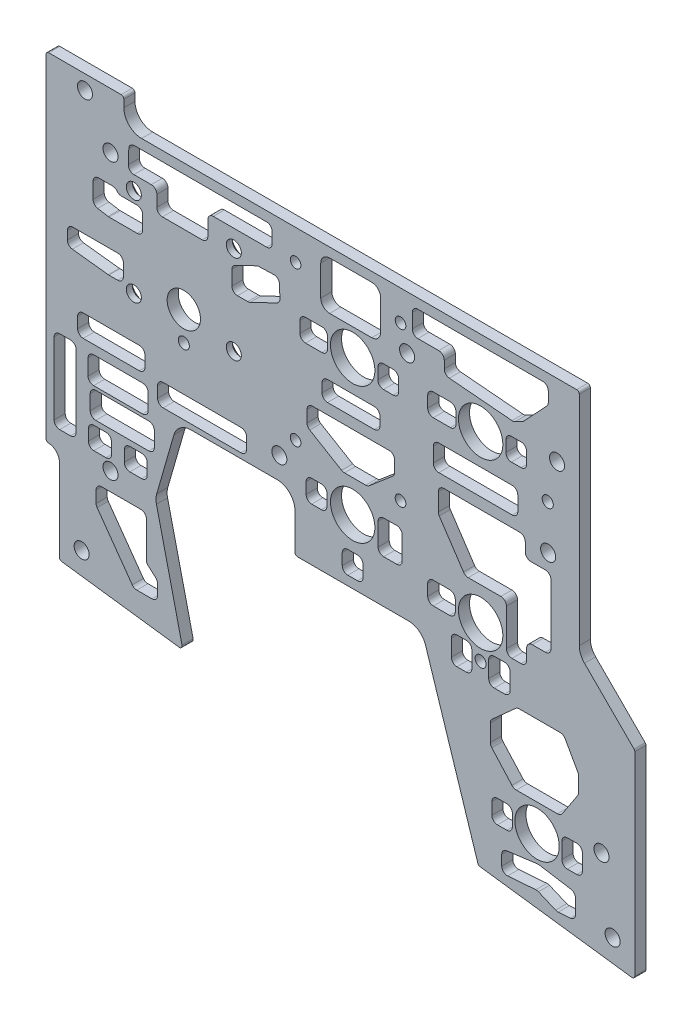
SolidWorks part; units mm, degrees
ref_plane "Front Plane" through (0, 0, 0) normal (0, 0, 1) x (1, 0, 0)
ref_plane "Top Plane" through (0, 0, 0) normal (0, 1, 0) x (1, 0, 0)
ref_plane "Right Plane" through (0, 0, 0) normal (1, 0, 0) x (0, 0, -1)
sketch "Sketch1" plane through (0, 0, 0) normal (0, 0, 1) x (1, 0, 0)
  line L16 (3.81, -91.8845) -> (3.81, -115.4033)
  line L17 (4.4725, -116.1588) -> (38.0231, -120.5758)
  line L18 (38.8645, -119.6465) -> (31.5446, -88.4134)
  line L19 (31.6093, -85.8475) -> (36.5334, -68.7608)
  line L20 (41.4148, -65.0875) -> (66.04, -65.0875)
  line L21 (71.12, -70.1675) -> (71.12, -80.518)
  line L22 (71.882, -81.28) -> (103.6122, -81.28)
  line L23 (108.4484, -84.805) -> (123.4233, -131.3792)
  line L24 (124.0493, -131.9014) -> (167.4135, -137.6104)
  line L25 (168.275, -136.8549) -> (168.275, -81.3036)
  line L26 (168.0518, -80.7647) -> (153.8879, -66.6008)
  line L27 (152.4, -63.0087) -> (152.4, -0.762)
  line L28 (151.638, 0) -> (27.305, 0)
  line L29 (22.225, 5.08) -> (22.225, 7.1755)
  line L30 (21.463, 7.9375) -> (0.762, 7.9375)
  line L31 (0, 7.1755) -> (0, -87.9495)
  line L32 (3.81, -91.8845) -> (3.81, -115.4033)
  line L33 (4.4725, -116.1588) -> (38.0231, -120.5758)
  line L34 (38.8645, -119.6465) -> (31.5446, -88.4134)
  line L35 (31.6093, -85.8475) -> (36.5334, -68.7608)
  line L36 (41.4148, -65.0875) -> (66.04, -65.0875)
  line L37 (71.12, -70.1675) -> (71.12, -80.518)
  line L38 (71.882, -81.28) -> (103.6122, -81.28)
  line L39 (108.4484, -84.805) -> (123.4233, -131.3792)
  line L40 (124.0493, -131.9014) -> (167.4135, -137.6104)
  line L41 (168.275, -136.8549) -> (168.275, -81.3036)
  line L42 (168.0518, -80.7647) -> (153.8879, -66.6008)
  line L43 (152.4, -63.0087) -> (152.4, -0.762)
  line L44 (151.638, 0) -> (27.305, 0)
  line L45 (22.225, 5.08) -> (22.225, 7.1755)
  line L46 (21.463, 7.9375) -> (0.762, 7.9375)
  line L47 (0, 7.1755) -> (0, -87.9495)
  arc A17 (3.81, -91.8845) -> (0.7374, -88.7112) centre (0.635, -91.8845) ccw
  arc A18 (3.81, -115.4033) -> (4.4725, -116.1588) centre (4.572, -115.4033) ccw
  arc A19 (38.0231, -120.5758) -> (38.8645, -119.6465) centre (38.1226, -119.8204) ccw
  arc A20 (31.6093, -85.8475) -> (31.5446, -88.4134) centre (36.4906, -87.2542) ccw
  arc A21 (41.4148, -65.0875) -> (36.5334, -68.7608) centre (41.4148, -70.1675) ccw
  arc A22 (71.12, -70.1675) -> (66.04, -65.0875) centre (66.04, -70.1675) ccw
  arc A23 (71.12, -80.518) -> (71.882, -81.28) centre (71.882, -80.518) ccw
  arc A24 (108.4484, -84.805) -> (103.6122, -81.28) centre (103.6122, -86.36) ccw
  arc A25 (123.4233, -131.3792) -> (124.0493, -131.9014) centre (124.1487, -131.1459) ccw
  arc A26 (167.4135, -137.6104) -> (168.275, -136.8549) centre (167.513, -136.8549) ccw
  arc A27 (168.275, -81.3036) -> (168.0518, -80.7647) centre (167.513, -81.3036) ccw
  arc A28 (152.4, -63.0087) -> (153.8879, -66.6008) centre (157.48, -63.0087) ccw
  arc A29 (152.4, -0.762) -> (151.638, 0) centre (151.638, -0.762) ccw
  arc A30 (22.225, 5.08) -> (27.305, 0) centre (27.305, 5.08) ccw
  arc A31 (22.225, 7.1755) -> (21.463, 7.9375) centre (21.463, 7.1755) ccw
  arc A32 (0.762, 7.9375) -> (0, 7.1755) centre (0.762, 7.1755) ccw
  arc A33 (0, -87.9495) -> (0.7374, -88.7112) centre (0.762, -87.9495) ccw
  arc A34 (3.81, -91.8845) -> (0.7374, -88.7112) centre (0.635, -91.8845) ccw
  arc A35 (3.81, -115.4033) -> (4.4725, -116.1588) centre (4.572, -115.4033) ccw
  arc A36 (38.0231, -120.5758) -> (38.8645, -119.6465) centre (38.1226, -119.8204) ccw
  arc A37 (31.6093, -85.8475) -> (31.5446, -88.4134) centre (36.4906, -87.2542) ccw
  arc A38 (41.4148, -65.0875) -> (36.5334, -68.7608) centre (41.4148, -70.1675) ccw
  arc A39 (71.12, -70.1675) -> (66.04, -65.0875) centre (66.04, -70.1675) ccw
  arc A40 (71.12, -80.518) -> (71.882, -81.28) centre (71.882, -80.518) ccw
  arc A41 (108.4484, -84.805) -> (103.6122, -81.28) centre (103.6122, -86.36) ccw
  arc A42 (123.4233, -131.3792) -> (124.0493, -131.9014) centre (124.1487, -131.1459) ccw
  arc A43 (167.4135, -137.6104) -> (168.275, -136.8549) centre (167.513, -136.8549) ccw
  arc A44 (168.275, -81.3036) -> (168.0518, -80.7647) centre (167.513, -81.3036) ccw
  arc A45 (152.4, -63.0087) -> (153.8879, -66.6008) centre (157.48, -63.0087) ccw
  arc A46 (152.4, -0.762) -> (151.638, 0) centre (151.638, -0.762) ccw
  arc A47 (22.225, 5.08) -> (27.305, 0) centre (27.305, 5.08) ccw
  arc A48 (22.225, 7.1755) -> (21.463, 7.9375) centre (21.463, 7.1755) ccw
  arc A49 (0.762, 7.9375) -> (0, 7.1755) centre (0.762, 7.1755) ccw
  arc A50 (0, -87.9495) -> (0.7374, -88.7112) centre (0.762, -87.9495) ccw
  dimension "D1" = 0
extrude "Boss-Extrude1" add sketch "Sketch1" against normal blind 3.175
hole_wizard "#6 Clearance Hole1" positions "Sketch3" profile "Sketch2" hole size "#6" standard "ANSI Inch" end condition through all
sketch "Sketch3" plane through (0, 0, -3.175) normal (0, 0, -1) x (-1, 0, 0)
  point P0 (-11.1125, 3.81)
  point P3 (-18.415, -7.9375)
  point P6 (-103.1875, -15.24)
  point P9 (-143.51, -44.45)
  point P12 (-158.75, -111.125)
  point P15 (-18.415, -86.741)
  point P18 (-66.675, -58.7375)
  point P21 (-10.16, -110.5028)
  point P25 (-146.05, -20.6375)
  point P28 (-161.925, -130.483)
sketch "Sketch2" plane through (11.1125, 3.81, -3.175) normal (1, 0, 0) x (0, 1, 0)
  line L0 (0, 0) -> (0, 3.175)
  line L1 (0, 3.175) -> (2.1526, 3.175)
  line L2 (2.1526, 3.175) -> (2.1526, 0)
  line L5 (2.1526, 0) -> (0, 0)
  line L11 (0, -6.35) -> (0, 107.95) construction
  dimension "Thru Hole Dia." = 4.3053
  dimension "Thru Hole Depth" = 3.175
sketch "Sketch4" plane through (0, 0, -3.175) normal (0, 0, -1) x (-1, 0, 0)
  circle A0 centre (-140.335, -115.57) radius 6.35
  circle A1 centre (-124.206, -71.4375) radius 6.35
  circle A2 centre (-87.63, -62.992) radius 6.35
  circle A3 centre (-87.63, -24.13) radius 6.35
  circle A4 centre (-124.206, -24.13) radius 6.35
  circle A5 centre (-124.206, -80.9625) radius 1.5875
  circle A6 centre (-39.37, -36.322) radius 4.7625
  dimension "D1" = 12.7
  dimension "D2" = 3.175
  dimension "D4" = 9.525
  dimension "D3" = 9.525
extrude "Cut-Extrude1" cut sketch "Sketch4" against normal through all
hole_wizard "CSK for #6 Flat Head Machine Screw (100)1" positions "Sketch6" profile "Sketch5" countersink size "#6" standard "ANSI Inch" end condition through all
sketch "Sketch6" plane through (0, 0, -3.175) normal (0, 0, -1) x (-1, 0, 0)
  point P0 (-53.6575, -14.097)
  point P2 (-25.0825, -14.097)
  point P4 (-25.0825, -39.497)
  point P6 (-53.6575, -39.497)
sketch "Sketch5" plane through (53.6575, -14.097, -3.175) normal (1, 0, 0) x (0, 1, 0)
  line L0 (0, 0) -> (0, 3.175)
  line L1 (0, 3.175) -> (2.1526, 3.175)
  line L2 (2.1526, 3.175) -> (2.1526, 1.4209)
  line L3 (2.1526, 1.4209) -> (3.846, 0)
  line L5 (3.846, 0) -> (0, 0)
  line L6 (-2.1526, 1.4209) -> (-3.846, 0) construction
  line L11 (0, -6.35) -> (0, 107.95) construction
  dimension "Thru Hole Dia." = 4.3053
  dimension "Thru Hole Depth" = 3.175
  dimension "Near C'Sink Dia." = 7.692
  dimension "Near C'Sink Angle" = 100
hole_wizard "#0 Clearance Hole1" positions "Sketch7" profile "Sketch8" hole size "#0" standard "ANSI Inch" end condition through all
sketch "Sketch7" plane through (0, 0, -9.525) normal (0, 0, -1) x (-1, 0, 0)
  point P0 (-39.37, -44.577)
sketch "Sketch8" plane through (39.37, -44.577, -9.525) normal (1, 0, 0) x (0, 1, 0)
  line L0 (0, 0) -> (0, 9.525)
  line L1 (0, 9.525) -> (0.9271, 9.525)
  line L2 (0.9271, 9.525) -> (0.9271, 0)
  line L3 (0.9271, 0) -> (0, 0)
  line L4 (0, -6.35) -> (0, 107.95) construction
  dimension "Thru Hole Dia." = 1.8542
  dimension "Thru Hole Depth" = 9.525
hole_wizard "1/8 (0.125) Diameter Hole1" positions "Sketch9" profile "Sketch10" hole size "1/8" standard "ANSI Inch" end condition through all
sketch "Sketch9" plane through (0, 0, 0) normal (0, 0, 1) x (1, 0, 0)
  point P0 (39.37, -44.577)
sketch "Sketch10" plane through (39.37, -44.577, 0) normal (1, 0, 0) x (0, -1, 0)
  line L0 (0, 0) -> (0, 3.175)
  line L1 (0, 3.175) -> (1.5875, 3.175)
  line L2 (1.5875, 3.175) -> (1.5875, 0)
  line L5 (1.5875, 0) -> (0, 0)
  line L11 (0, -6.35) -> (0, 107.95) construction
  dimension "Thru Hole Dia." = 3.175
  dimension "Thru Hole Depth" = 3.175
sketch "Sketch17" plane through (0, 0, 0) normal (0, 0, -1) x (-1, 0, 0)
  line L0 (-141.9544, -2.7948) -> (-106.2662, -2.7948)
  line L1 (-104.6787, -4.3823) -> (-104.6787, -8.4606)
  line L2 (-106.2662, -10.0481) -> (-112.2209, -10.0481)
  line L3 (-113.8084, -11.6356) -> (-113.8084, -13.7762)
  line L4 (-115.259, -15.3578) -> (-133.159, -16.9076)
  line L5 (-134.0131, -16.7423) -> (-136.0874, -15.6921)
  line L6 (-136.5298, -15.36) -> (-143.114, -8.3185)
  line L7 (-143.5419, -7.2342) -> (-143.5419, -4.3823)
  line L8 (-93.0669, -2.7076) -> (-81.0441, -2.7076)
  line L9 (-78.5041, -5.2476) -> (-78.5041, -13.8956)
  line L10 (-81.0441, -16.4356) -> (-93.0669, -16.4356)
  line L11 (-95.6069, -13.8956) -> (-95.6069, -5.2476)
  line L12 (-72.5612, -22.437) -> (-72.5612, -25.637)
  line L13 (-74.1487, -27.2245) -> (-78.851, -27.2245)
  line L14 (-80.4385, -25.637) -> (-80.4385, -22.437)
  line L15 (-74.1487, -20.8495) -> (-78.851, -20.8495)
  line L16 (-99.2018, -21.1963) -> (-96.4213, -21.1963)
  line L17 (-94.8338, -22.7838) -> (-94.8338, -25.9818)
  line L18 (-96.4213, -27.5693) -> (-99.2018, -27.5693)
  line L19 (-100.7893, -25.9818) -> (-100.7893, -22.7838)
  line L20 (-109.0792, -22.6549) -> (-109.0792, -25.8549)
  line L21 (-110.6667, -27.4424) -> (-115.5536, -27.4424)
  line L22 (-117.1411, -25.8549) -> (-117.1411, -22.6549)
  line L23 (-110.6667, -21.0674) -> (-115.5536, -21.0674)
  line L24 (-135.7738, -20.8814) -> (-132.9933, -20.8814)
  line L25 (-131.4058, -22.4689) -> (-131.4058, -25.667)
  line L26 (-132.9933, -27.2545) -> (-135.7738, -27.2545)
  line L27 (-137.3613, -25.667) -> (-137.3613, -22.4689)
  line L28 (-93.8189, -33.0853) -> (-80.4385, -33.0853)
  line L29 (-78.851, -34.6728) -> (-78.851, -37.1954)
  line L30 (-80.4385, -38.7829) -> (-93.8189, -38.7829)
  line L31 (-95.4064, -34.6728) -> (-95.4064, -37.1954)
  line L32 (-133.2346, -32.9063) -> (-112.2542, -32.9063)
  line L33 (-110.6667, -34.4938) -> (-110.6667, -38.6545)
  line L34 (-112.2542, -40.242) -> (-133.2346, -40.242)
  line L35 (-134.8221, -38.6545) -> (-134.8221, -34.4938)
  line L36 (-98.0498, -41.8469) -> (-76.1717, -41.8469)
  line L37 (-74.5842, -43.4344) -> (-74.5842, -46.7771)
  line L38 (-75.3596, -48.1412) -> (-84.4657, -53.5626)
  line L39 (-85.2778, -53.7861) -> (-91.3474, -53.7861)
  line L40 (-92.3756, -53.4081) -> (-99.0779, -47.711)
  line L41 (-99.6373, -46.5014) -> (-99.6373, -43.4344)
  line L42 (-135.3789, -43.4344) -> (-113.699, -43.4344)
  line L43 (-112.1115, -45.0219) -> (-112.1115, -50.0429)
  line L44 (-112.3789, -50.9245) -> (-119.3229, -61.3222)
  line L45 (-120.6431, -62.0281) -> (-129.9871, -62.0281)
  line L47 (-136.9664, -47.5212) -> (-136.9664, -45.0219)
  line L48 (-55.7285, -57.3176) -> (-33.4587, -57.3176)
  line L49 (-31.8712, -58.9051) -> (-31.8712, -62.02)
  line L50 (-33.4587, -63.6075) -> (-55.7285, -63.6075)
  line L51 (-57.316, -62.02) -> (-57.316, -58.9051)
  line L52 (-78.7021, -59.8174) -> (-75.9216, -59.8174)
  line L53 (-74.3341, -61.4049) -> (-74.3341, -64.603)
  line L54 (-75.9216, -66.1905) -> (-78.7021, -66.1905)
  line L55 (-80.2896, -64.603) -> (-80.2896, -61.4049)
  line L56 (-89.0189, -72.2548) -> (-86.2384, -72.2548)
  line L57 (-84.6509, -73.8423) -> (-84.6509, -77.0403)
  line L58 (-86.2384, -78.6278) -> (-89.0189, -78.6278)
  line L59 (-90.6064, -77.0403) -> (-90.6064, -73.8423)
  line L60 (-109.0756, -69.248) -> (-109.0756, -72.448)
  line L61 (-110.6631, -74.0355) -> (-115.3654, -74.0355)
  line L62 (-116.9529, -72.448) -> (-116.9529, -69.248)
  line L63 (-110.6631, -67.6605) -> (-115.3654, -67.6605)
  line L64 (-148.3701, -88.0766) -> (-151.9572, -94.4661)
  line L65 (-152.1698, -95.2794) -> (-152.1698, -99.4916)
  line L66 (-151.8961, -100.4052) -> (-147.5598, -106.9917)
  line L67 (-138.5539, -49.1087) -> (-142.7058, -49.1087)
  line L68 (-146.1721, -107.7395) -> (-134.3926, -107.7395)
  line L69 (-144.2933, -50.6962) -> (-144.2933, -67.8867)
  line L70 (-133.1575, -107.1893) -> (-127.3956, -100.785)
  line L71 (-126.9693, -99.6738) -> (-126.9693, -94.8668)
  line L72 (-127.5195, -93.6317) -> (-134.1629, -87.6548)
  line L73 (-135.2742, -87.2285) -> (-146.9213, -87.2285)
  line L74 (-137.3613, -71.0617) -> (-137.3613, -74.1715)
  line L75 (-135.7738, -75.759) -> (-133.1621, -75.759)
  line L76 (-131.5746, -74.1715) -> (-131.5746, -63.6156)
  line L78 (-132.6264, -79.3569) -> (-132.6264, -84.055)
  line L79 (-131.0389, -85.6425) -> (-128.0874, -85.6425)
  line L80 (-126.4999, -84.055) -> (-126.4999, -79.3653)
  line L81 (-128.0829, -77.7778) -> (-131.0344, -77.7694)
  line L82 (-121.6938, -79.414) -> (-121.6938, -84.1113)
  line L83 (-120.1063, -85.6988) -> (-117.4258, -85.6988)
  line L84 (-115.8383, -84.1113) -> (-115.8383, -79.4216)
  line L85 (-117.4212, -77.8341) -> (-120.1018, -77.8265)
  line L86 (-101.7978, -60.9375) -> (-101.7978, -67.3473)
  line L87 (-100.2103, -68.9348) -> (-96.4976, -68.9348)
  line L88 (-94.9101, -67.3473) -> (-94.9101, -60.9481)
  line L89 (-96.4931, -59.3606) -> (-100.2058, -59.35)
  line L90 (-153.2801, -113.8454) -> (-153.2801, -118.4115)
  line L91 (-151.6926, -119.999) -> (-149.0121, -119.999)
  line L92 (-147.4246, -118.4115) -> (-147.4246, -113.853)
  line L93 (-149.0076, -112.2655) -> (-151.6881, -112.2579)
  line L94 (-133.2696, -114.0603) -> (-133.2696, -117.4522)
  line L95 (-131.6821, -119.0397) -> (-129.0016, -119.0397)
  line L96 (-127.4141, -117.4522) -> (-127.4141, -114.0679)
  line L97 (-128.997, -112.4804) -> (-131.6776, -112.4728)
  line L98 (-150.0084, -124.4751) -> (-140.8902, -122.9925)
  line L99 (-140.4256, -122.9858) -> (-131.6139, -124.1607)
  line L100 (-130.2362, -125.7343) -> (-130.2362, -128.6297)
  line L101 (-131.9392, -130.213) -> (-139.9781, -129.6268)
  line L102 (-140.7126, -129.7482) -> (-145.6471, -131.838)
  line L103 (-146.3817, -131.9595) -> (-149.8691, -131.7052)
  line L104 (-151.3411, -130.1219) -> (-151.3411, -126.042)
  line L105 (-63.0404, -2.7948) -> (-25.2277, -2.7948)
  line L106 (-23.641, -4.3315) -> (-23.5105, -8.4099)
  line L107 (-25.0972, -10.0481) -> (-30.0725, -10.0481)
  line L108 (-31.66, -11.6356) -> (-31.66, -14.8481)
  line L109 (-33.2475, -16.4356) -> (-44.6401, -16.4356)
  line L110 (-46.2276, -14.8481) -> (-46.2276, -10.6224)
  line L111 (-47.8151, -9.0349) -> (-63.0404, -9.0349)
  line L112 (-64.6279, -7.4474) -> (-64.6279, -4.3823)
  line L113 (-14.7591, -23.5708) -> (-17.7234, -24.0903)
  line L114 (-17.9974, -24.1142) -> (-26.0381, -24.1142)
  line L115 (-27.6256, -22.5267) -> (-27.6256, -18.7366)
  line L116 (-26.0381, -17.1491) -> (-21.5632, -17.1491)
  line L117 (-20.4504, -16.6939) -> (-20.1204, -16.3695)
  line L118 (-19.0076, -15.9142) -> (-15.0331, -15.9142)
  line L119 (-13.4456, -17.5017) -> (-13.4456, -22.0071)
  line L120 (-7.6875, -31.7843) -> (-20.4927, -31.7843)
  line L121 (-22.0802, -33.3718) -> (-22.0802, -36.9105)
  line L122 (-20.4927, -38.498) -> (-17.9504, -38.498)
  line L123 (-17.7686, -38.4875) -> (-7.5058, -37.3048)
  line L124 (-6.1, -35.7277) -> (-6.1, -33.3718)
  line L125 (-54.0177, -18.0353) -> (-60.157, -15.0963)
  line L126 (-60.7931, -14.9415) -> (-65.0805, -14.8081)
  line L127 (-66.7166, -16.3454) -> (-66.8282, -19.9294)
  line L128 (-65.9269, -21.4107) -> (-58.3022, -25.0607)
  line L129 (-57.6167, -25.2163) -> (-54.7032, -25.2163)
  line L130 (-53.1157, -23.6288) -> (-53.1157, -19.4672)
  line L131 (-24.6224, -111.8142) -> (-14.5986, -97.7476)
  line L132 (-14.304, -96.8263) -> (-14.304, -93.5113)
  line L133 (-2.2976, -61.6269) -> (-2.2976, -82.1859)
  line L134 (-3.8851, -83.7734) -> (-6.9926, -83.7734)
  line L135 (-8.5801, -82.1859) -> (-8.5801, -61.6269)
  line L136 (-6.9926, -60.0394) -> (-3.8851, -60.0394)
  line L137 (-15.8915, -91.9238) -> (-27.0858, -91.9238)
  line L138 (-28.6733, -93.5113) -> (-28.6733, -103.656)
  line L139 (-29.2117, -104.8474) -> (-31.3328, -106.7152)
  line L140 (-31.8712, -107.9067) -> (-31.8712, -110.8929)
  line L141 (-30.2837, -112.4804) -> (-25.9153, -112.4804)
  line L142 (-26.655, -51.5392) -> (-10.6039, -51.5392)
  line L143 (-9.0164, -53.1267) -> (-9.0164, -56.2416)
  line L144 (-10.6039, -57.8291) -> (-26.655, -57.8291)
  line L145 (-28.2425, -56.2416) -> (-28.2425, -53.1267)
  line L146 (-27.6052, -60.385) -> (-13.5866, -60.385)
  line L147 (-11.9991, -61.9725) -> (-11.9991, -66.4544)
  line L148 (-13.5866, -68.0419) -> (-27.6052, -68.0419)
  line L149 (-29.1927, -66.4544) -> (-29.1927, -61.9725)
  line L150 (-29.347, -68.9032) -> (-14.2014, -68.9032)
  line L151 (-12.6139, -70.4907) -> (-12.6139, -74.7412)
  line L152 (-14.2014, -76.3287) -> (-29.347, -76.3287)
  line L153 (-30.9345, -74.7412) -> (-30.9345, -70.4907)
  line L154 (-27.3287, -77.9076) -> (-23.9481, -77.9076)
  line L155 (-22.3606, -79.4951) -> (-22.3606, -82.61)
  line L156 (-23.9481, -84.1975) -> (-27.3287, -84.1975)
  line L157 (-28.9162, -82.61) -> (-28.9162, -79.4951)
  line L158 (-17.1192, -77.821) -> (-13.667, -77.821)
  line L159 (-12.0795, -79.4085) -> (-12.0795, -82.5234)
  line L160 (-13.667, -84.1109) -> (-17.1192, -84.1109)
  line L161 (-18.7067, -82.5234) -> (-18.7067, -79.4085)
  line L162 (-142.7058, -69.4742) -> (-138.9488, -69.4742)
  arc A0 (-106.2662, -2.7948) -> (-104.6787, -4.3823) centre (-106.2662, -4.3823) cw
  arc A1 (-104.6787, -8.4606) -> (-106.2662, -10.0481) centre (-106.2662, -8.4606) cw
  arc A2 (-112.2209, -10.0481) -> (-113.8084, -11.6356) centre (-112.2209, -11.6356) ccw
  arc A3 (-113.8084, -13.7762) -> (-115.259, -15.3578) centre (-115.3959, -13.7762) cw
  arc A4 (-133.159, -16.9076) -> (-134.0131, -16.7423) centre (-133.296, -15.326) cw
  arc A5 (-136.0874, -15.6921) -> (-136.5298, -15.36) centre (-135.3703, -14.2758) cw
  arc A6 (-143.114, -8.3185) -> (-143.5419, -7.2342) centre (-141.9544, -7.2342) cw
  arc A7 (-141.9544, -2.7948) -> (-143.5419, -4.3823) centre (-141.9544, -4.3823) ccw
  arc A8 (-81.0441, -2.7076) -> (-78.5041, -5.2476) centre (-81.0441, -5.2476) cw
  arc A9 (-78.5041, -13.8956) -> (-81.0441, -16.4356) centre (-81.0441, -13.8956) cw
  arc A10 (-93.0669, -16.4356) -> (-95.6069, -13.8956) centre (-93.0669, -13.8956) cw
  arc A11 (-93.0669, -2.7076) -> (-95.6069, -5.2476) centre (-93.0669, -5.2476) ccw
  arc A12 (-72.5612, -22.437) -> (-74.1487, -20.8495) centre (-74.1487, -22.437) ccw
  arc A13 (-72.5612, -25.637) -> (-74.1487, -27.2245) centre (-74.1487, -25.637) cw
  arc A14 (-78.851, -27.2245) -> (-80.4385, -25.637) centre (-78.851, -25.637) cw
  arc A15 (-80.4385, -22.437) -> (-78.851, -20.8495) centre (-78.851, -22.437) cw
  arc A16 (-96.4213, -21.1963) -> (-94.8338, -22.7838) centre (-96.4213, -22.7838) cw
  arc A17 (-94.8338, -25.9818) -> (-96.4213, -27.5693) centre (-96.4213, -25.9818) cw
  arc A18 (-99.2018, -27.5693) -> (-100.7893, -25.9818) centre (-99.2018, -25.9818) cw
  arc A19 (-99.2018, -21.1963) -> (-100.7893, -22.7838) centre (-99.2018, -22.7838) ccw
  arc A20 (-109.0792, -22.6549) -> (-110.6667, -21.0674) centre (-110.6667, -22.6549) ccw
  arc A21 (-109.0792, -25.8549) -> (-110.6667, -27.4424) centre (-110.6667, -25.8549) cw
  arc A22 (-115.5536, -27.4424) -> (-117.1411, -25.8549) centre (-115.5536, -25.8549) cw
  arc A23 (-117.1411, -22.6549) -> (-115.5536, -21.0674) centre (-115.5536, -22.6549) cw
  arc A24 (-132.9933, -20.8814) -> (-131.4058, -22.4689) centre (-132.9933, -22.4689) cw
  arc A25 (-131.4058, -25.667) -> (-132.9933, -27.2545) centre (-132.9933, -25.667) cw
  arc A26 (-135.7738, -27.2545) -> (-137.3613, -25.667) centre (-135.7738, -25.667) cw
  arc A27 (-135.7738, -20.8814) -> (-137.3613, -22.4689) centre (-135.7738, -22.4689) ccw
  arc A28 (-80.4385, -33.0853) -> (-78.851, -34.6728) centre (-80.4385, -34.6728) cw
  arc A29 (-78.851, -37.1954) -> (-80.4385, -38.7829) centre (-80.4385, -37.1954) cw
  arc A30 (-93.8189, -38.7829) -> (-95.4064, -37.1954) centre (-93.8189, -37.1954) cw
  arc A31 (-93.8189, -33.0853) -> (-95.4064, -34.6728) centre (-93.8189, -34.6728) ccw
  arc A32 (-112.2542, -32.9063) -> (-110.6667, -34.4938) centre (-112.2542, -34.4938) cw
  arc A33 (-110.6667, -38.6545) -> (-112.2542, -40.242) centre (-112.2542, -38.6545) cw
  arc A34 (-133.2346, -40.242) -> (-134.8221, -38.6545) centre (-133.2346, -38.6545) cw
  arc A35 (-133.2346, -32.9063) -> (-134.8221, -34.4938) centre (-133.2346, -34.4938) ccw
  arc A36 (-91.3474, -53.7861) -> (-92.3756, -53.4081) centre (-91.3474, -52.1986) cw
  arc A37 (-84.4657, -53.5626) -> (-85.2778, -53.7861) centre (-85.2778, -52.1986) cw
  arc A38 (-74.5842, -46.7771) -> (-75.3596, -48.1412) centre (-76.1717, -46.7771) cw
  arc A39 (-76.1717, -41.8469) -> (-74.5842, -43.4344) centre (-76.1717, -43.4344) cw
  arc A40 (-98.0498, -41.8469) -> (-99.6373, -43.4344) centre (-98.0498, -43.4344) ccw
  arc A41 (-99.0779, -47.711) -> (-99.6373, -46.5014) centre (-98.0498, -46.5014) cw
  arc A42 (-113.699, -43.4344) -> (-112.1115, -45.0219) centre (-113.699, -45.0219) cw
  arc A43 (-112.1115, -50.0429) -> (-112.3789, -50.9245) centre (-113.699, -50.0429) cw
  arc A44 (-119.3229, -61.3222) -> (-120.6431, -62.0281) centre (-120.6431, -60.4406) cw
  arc A47 (-135.3789, -43.4344) -> (-136.9664, -45.0219) centre (-135.3789, -45.0219) ccw
  arc A48 (-33.4587, -57.3176) -> (-31.8712, -58.9051) centre (-33.4587, -58.9051) cw
  arc A49 (-31.8712, -62.02) -> (-33.4587, -63.6075) centre (-33.4587, -62.02) cw
  arc A50 (-55.7285, -63.6075) -> (-57.316, -62.02) centre (-55.7285, -62.02) cw
  arc A51 (-55.7285, -57.3176) -> (-57.316, -58.9051) centre (-55.7285, -58.9051) ccw
  arc A52 (-75.9216, -59.8174) -> (-74.3341, -61.4049) centre (-75.9216, -61.4049) cw
  arc A53 (-74.3341, -64.603) -> (-75.9216, -66.1905) centre (-75.9216, -64.603) cw
  arc A54 (-78.7021, -66.1905) -> (-80.2896, -64.603) centre (-78.7021, -64.603) cw
  arc A55 (-78.7021, -59.8174) -> (-80.2896, -61.4049) centre (-78.7021, -61.4049) ccw
  arc A56 (-86.2384, -72.2548) -> (-84.6509, -73.8423) centre (-86.2384, -73.8423) cw
  arc A57 (-84.6509, -77.0403) -> (-86.2384, -78.6278) centre (-86.2384, -77.0403) cw
  arc A58 (-89.0189, -78.6278) -> (-90.6064, -77.0403) centre (-89.0189, -77.0403) cw
  arc A59 (-89.0189, -72.2548) -> (-90.6064, -73.8423) centre (-89.0189, -73.8423) ccw
  arc A60 (-109.0756, -69.248) -> (-110.6631, -67.6605) centre (-110.6631, -69.248) ccw
  arc A61 (-109.0756, -72.448) -> (-110.6631, -74.0355) centre (-110.6631, -72.448) cw
  arc A62 (-115.3654, -74.0355) -> (-116.9529, -72.448) centre (-115.3654, -72.448) cw
  arc A63 (-116.9529, -69.248) -> (-115.3654, -67.6605) centre (-115.3654, -69.248) cw
  arc A64 (-134.1629, -87.6548) -> (-135.2742, -87.2285) centre (-135.2742, -88.8899) ccw
  arc A65 (-126.9693, -94.8668) -> (-127.5195, -93.6317) centre (-128.6308, -94.8668) ccw
  arc A66 (-127.3956, -100.785) -> (-126.9693, -99.6738) centre (-128.6308, -99.6738) ccw
  arc A67 (-134.3926, -107.7395) -> (-133.1575, -107.1893) centre (-134.3926, -106.0781) ccw
  arc A68 (-147.5598, -106.9917) -> (-146.1721, -107.7395) centre (-146.1721, -106.0781) ccw
  arc A69 (-152.1698, -99.4916) -> (-151.8961, -100.4052) centre (-150.5084, -99.4916) ccw
  arc A70 (-151.9572, -94.4661) -> (-152.1698, -95.2794) centre (-150.5084, -95.2794) ccw
  arc A71 (-148.3701, -88.0766) -> (-146.9213, -87.2285) centre (-146.9213, -88.8899) cw
  arc A74 (-133.1621, -75.759) -> (-131.5746, -74.1715) centre (-133.1621, -74.1715) ccw
  arc A75 (-137.3613, -74.1715) -> (-135.7738, -75.759) centre (-135.7738, -74.1715) ccw
  arc A76 (-132.6264, -79.3569) -> (-131.0344, -77.7694) centre (-131.0389, -79.3569) cw
  arc A77 (-126.4999, -79.3653) -> (-128.0829, -77.7778) centre (-128.0874, -79.3653) ccw
  arc A78 (-128.0874, -85.6425) -> (-126.4999, -84.055) centre (-128.0874, -84.055) ccw
  arc A79 (-132.6264, -84.055) -> (-131.0389, -85.6425) centre (-131.0389, -84.055) ccw
  arc A80 (-121.6938, -79.414) -> (-120.1018, -77.8265) centre (-120.1063, -79.414) cw
  arc A81 (-115.8383, -79.4216) -> (-117.4212, -77.8341) centre (-117.4258, -79.4216) ccw
  arc A82 (-117.4258, -85.6988) -> (-115.8383, -84.1113) centre (-117.4258, -84.1113) ccw
  arc A83 (-121.6938, -84.1113) -> (-120.1063, -85.6988) centre (-120.1063, -84.1113) ccw
  arc A84 (-101.7978, -60.9375) -> (-100.2058, -59.35) centre (-100.2103, -60.9375) cw
  arc A85 (-94.9101, -60.9481) -> (-96.4931, -59.3606) centre (-96.4976, -60.9481) ccw
  arc A86 (-96.4976, -68.9348) -> (-94.9101, -67.3473) centre (-96.4976, -67.3473) ccw
  arc A87 (-101.7978, -67.3473) -> (-100.2103, -68.9348) centre (-100.2103, -67.3473) ccw
  arc A88 (-153.2801, -113.8454) -> (-151.6881, -112.2579) centre (-151.6926, -113.8454) cw
  arc A89 (-147.4246, -113.853) -> (-149.0076, -112.2655) centre (-149.0121, -113.853) ccw
  arc A90 (-149.0121, -119.999) -> (-147.4246, -118.4115) centre (-149.0121, -118.4115) ccw
  arc A91 (-153.2801, -118.4115) -> (-151.6926, -119.999) centre (-151.6926, -118.4115) ccw
  arc A92 (-133.2696, -114.0603) -> (-131.6776, -112.4728) centre (-131.6821, -114.0603) cw
  arc A93 (-127.4141, -114.0679) -> (-128.997, -112.4804) centre (-129.0016, -114.0679) ccw
  arc A94 (-129.0016, -119.0397) -> (-127.4141, -117.4522) centre (-129.0016, -117.4522) ccw
  arc A95 (-133.2696, -117.4522) -> (-131.6821, -119.0397) centre (-131.6821, -117.4522) ccw
  arc A96 (-140.8902, -122.9925) -> (-140.4256, -122.9858) centre (-140.6354, -124.5594) cw
  arc A97 (-131.6139, -124.1607) -> (-130.2362, -125.7343) centre (-131.8237, -125.7343) cw
  arc A98 (-130.2362, -128.6297) -> (-131.9392, -130.213) centre (-131.8237, -128.6297) cw
  arc A99 (-139.9781, -129.6268) -> (-140.7126, -129.7482) centre (-140.0935, -131.2101) ccw
  arc A100 (-145.6471, -131.838) -> (-146.3817, -131.9595) centre (-146.2662, -130.3762) cw
  arc A101 (-149.8691, -131.7052) -> (-151.3411, -130.1219) centre (-149.7536, -130.1219) cw
  arc A102 (-150.0084, -124.4751) -> (-151.3411, -126.042) centre (-149.7536, -126.042) ccw
  arc A103 (-63.0404, -2.7948) -> (-64.6279, -4.3823) centre (-63.0404, -4.3823) ccw
  arc A104 (-25.2277, -2.7948) -> (-23.641, -4.3315) centre (-25.2277, -4.3823) cw
  arc A105 (-23.5105, -8.4099) -> (-25.0972, -10.0481) centre (-25.0972, -8.4606) cw
  arc A106 (-30.0725, -10.0481) -> (-31.66, -11.6356) centre (-30.0725, -11.6356) ccw
  arc A107 (-31.66, -14.8481) -> (-33.2475, -16.4356) centre (-33.2475, -14.8481) cw
  arc A108 (-44.6401, -16.4356) -> (-46.2276, -14.8481) centre (-44.6401, -14.8481) cw
  arc A109 (-46.2276, -10.6224) -> (-47.8151, -9.0349) centre (-47.8151, -10.6224) ccw
  arc A110 (-63.0404, -9.0349) -> (-64.6279, -7.4474) centre (-63.0404, -7.4474) cw
  arc A111 (-23.9481, -77.9076) -> (-22.3606, -79.4951) centre (-23.9481, -79.4951) cw
  arc A112 (-21.5632, -17.1491) -> (-20.4504, -16.6939) centre (-21.5632, -15.5616) ccw
  arc A113 (-20.1204, -16.3695) -> (-19.0076, -15.9142) centre (-19.0076, -17.5017) cw
  arc A114 (-15.0331, -15.9142) -> (-13.4456, -17.5017) centre (-15.0331, -17.5017) cw
  arc A115 (-14.7591, -23.5708) -> (-13.4456, -22.0071) centre (-15.0331, -22.0071) ccw
  arc A116 (-17.7234, -24.0903) -> (-17.9974, -24.1142) centre (-17.9974, -22.5267) cw
  arc A117 (-26.0381, -24.1142) -> (-27.6256, -22.5267) centre (-26.0381, -22.5267) cw
  arc A118 (-27.6256, -18.7366) -> (-26.0381, -17.1491) centre (-26.0381, -18.7366) cw
  arc A119 (-20.4927, -31.7843) -> (-22.0802, -33.3718) centre (-20.4927, -33.3718) ccw
  arc A120 (-22.0802, -36.9105) -> (-20.4927, -38.498) centre (-20.4927, -36.9105) ccw
  arc A121 (-17.9504, -38.498) -> (-17.7686, -38.4875) centre (-17.9504, -36.9105) ccw
  arc A122 (-7.5058, -37.3048) -> (-6.1, -35.7277) centre (-7.6875, -35.7277) ccw
  arc A123 (-7.6875, -31.7843) -> (-6.1, -33.3718) centre (-7.6875, -33.3718) cw
  arc A124 (-58.3022, -25.0607) -> (-57.6167, -25.2163) centre (-57.6167, -23.6288) ccw
  arc A125 (-54.7032, -25.2163) -> (-53.1157, -23.6288) centre (-54.7032, -23.6288) ccw
  arc A126 (-54.0177, -18.0353) -> (-53.1157, -19.4672) centre (-54.7032, -19.4672) cw
  arc A127 (-60.157, -15.0963) -> (-60.7931, -14.9415) centre (-60.8425, -16.5282) ccw
  arc A128 (-65.0805, -14.8081) -> (-66.7166, -16.3454) centre (-65.1299, -16.3948) ccw
  arc A129 (-66.8282, -19.9294) -> (-65.9269, -21.4107) centre (-65.2414, -19.9788) ccw
  arc A130 (-6.9926, -83.7734) -> (-8.5801, -82.1859) centre (-6.9926, -82.1859) cw
  arc A131 (-2.2976, -82.1859) -> (-3.8851, -83.7734) centre (-3.8851, -82.1859) cw
  arc A132 (-3.8851, -60.0394) -> (-2.2976, -61.6269) centre (-3.8851, -61.6269) cw
  arc A133 (-8.5801, -61.6269) -> (-6.9926, -60.0394) centre (-6.9926, -61.6269) cw
  arc A134 (-14.304, -93.5113) -> (-15.8915, -91.9238) centre (-15.8915, -93.5113) ccw
  arc A135 (-14.5986, -97.7476) -> (-14.304, -96.8263) centre (-15.8915, -96.8263) ccw
  arc A136 (-24.6224, -111.8142) -> (-25.9153, -112.4804) centre (-25.9153, -110.8929) cw
  arc A137 (-31.8712, -110.8929) -> (-30.2837, -112.4804) centre (-30.2837, -110.8929) ccw
  arc A138 (-31.3328, -106.7152) -> (-31.8712, -107.9067) centre (-30.2837, -107.9067) ccw
  arc A139 (-28.6733, -103.656) -> (-29.2117, -104.8474) centre (-30.2608, -103.656) cw
  arc A140 (-27.0858, -91.9238) -> (-28.6733, -93.5113) centre (-27.0858, -93.5113) ccw
  arc A141 (-10.6039, -51.5392) -> (-9.0164, -53.1267) centre (-10.6039, -53.1267) cw
  arc A142 (-9.0164, -56.2416) -> (-10.6039, -57.8291) centre (-10.6039, -56.2416) cw
  arc A143 (-26.655, -57.8291) -> (-28.2425, -56.2416) centre (-26.655, -56.2416) cw
  arc A144 (-26.655, -51.5392) -> (-28.2425, -53.1267) centre (-26.655, -53.1267) ccw
  arc A145 (-13.5866, -60.385) -> (-11.9991, -61.9725) centre (-13.5866, -61.9725) cw
  arc A146 (-11.9991, -66.4544) -> (-13.5866, -68.0419) centre (-13.5866, -66.4544) cw
  arc A147 (-27.6052, -68.0419) -> (-29.1927, -66.4544) centre (-27.6052, -66.4544) cw
  arc A148 (-27.6052, -60.385) -> (-29.1927, -61.9725) centre (-27.6052, -61.9725) ccw
  arc A149 (-14.2014, -68.9032) -> (-12.6139, -70.4907) centre (-14.2014, -70.4907) cw
  arc A150 (-12.6139, -74.7412) -> (-14.2014, -76.3287) centre (-14.2014, -74.7412) cw
  arc A151 (-29.347, -76.3287) -> (-30.9345, -74.7412) centre (-29.347, -74.7412) cw
  arc A152 (-29.347, -68.9032) -> (-30.9345, -70.4907) centre (-29.347, -70.4907) ccw
  arc A153 (-22.3606, -82.61) -> (-23.9481, -84.1975) centre (-23.9481, -82.61) cw
  arc A154 (-27.3287, -84.1975) -> (-28.9162, -82.61) centre (-27.3287, -82.61) cw
  arc A155 (-27.3287, -77.9076) -> (-28.9162, -79.4951) centre (-27.3287, -79.4951) ccw
  arc A156 (-13.667, -77.821) -> (-12.0795, -79.4085) centre (-13.667, -79.4085) cw
  arc A157 (-12.0795, -82.5234) -> (-13.667, -84.1109) centre (-13.667, -82.5234) cw
  arc A158 (-17.1192, -84.1109) -> (-18.7067, -82.5234) centre (-17.1192, -82.5234) cw
  arc A159 (-17.1192, -77.821) -> (-18.7067, -79.4085) centre (-17.1192, -79.4085) ccw
  circle A160 centre (-143.3865, -31.863) radius 1.5875
  arc A161 (-136.9664, -47.5212) -> (-138.5539, -49.1087) centre (-138.5539, -47.5212) cw
  arc A162 (-142.7058, -49.1087) -> (-144.2933, -50.6962) centre (-142.7058, -50.6962) ccw
  arc A163 (-144.2933, -67.8867) -> (-142.7058, -69.4742) centre (-142.7058, -67.8867) ccw
  arc A164 (-137.3613, -71.0617) -> (-138.9488, -69.4742) centre (-138.9488, -71.0617) ccw
  arc A165 (-131.5746, -63.6156) -> (-129.9871, -62.0281) centre (-129.9871, -63.6156) cw
  point P212 (-133.6525, -107.7395)
  point P215 (-147.0675, -107.7395)
  dimension "D1" = 1.5875
  dimension "D2" = 2.54
  dimension "D3" = 1.5875
  dimension "D4" = 1.5875
  dimension "D5" = 1.5875
  dimension "D6" = 1.5875
  dimension "D7" = 1.5875
  dimension "D8" = 1.5875
  dimension "D9" = 1.5875
  dimension "D10" = 1.5875
  dimension "D11" = 1.6614
  dimension "D12" = 1.5875
  dimension "D13" = 1.5875
  dimension "D14" = 1.5875
  dimension "D15" = 1.5875
  dimension "D16" = 1.5875
  dimension "D17" = 1.5875
  dimension "D18" = 1.5875
  dimension "D19" = 1.5875
  dimension "D20" = 3.175
extrude "Backlighting Holes" cut sketch "Sketch17" along normal through all
sketch "Sketch20" plane through (0, 0, 0) normal (0, 0, 1) x (1, 0, 0)
  line L2 (71.3117, -8.663) -> (101.3117, -8.663) construction
  line L3 (101.3117, -8.663) -> (101.3117, -52.663) construction
  line L4 (101.3117, -52.663) -> (71.3117, -52.663) construction
  line L5 (71.3117, -52.663) -> (71.3117, -8.663) construction
  line L6 (71.3117, -8.663) -> (71.3117, 0) construction
  line L8 (152.4, -8.663) -> (101.3117, -8.663) construction
  line L9 (152.4, -63.0087) -> (152.4, -0.762) construction
  circle A0 centre (101.3117, -8.663) radius 1.52
  circle A1 centre (71.3117, -8.663) radius 1.52
  circle A2 centre (101.3117, -52.663) radius 1.52
  circle A3 centre (71.3117, -52.663) radius 1.52
  dimension "D2" = 51.0883
  dimension "D3" = 30
  dimension "D4" = 44
extrude "Switch PCB Mounting Holes" cut sketch "Sketch20" against normal through all
